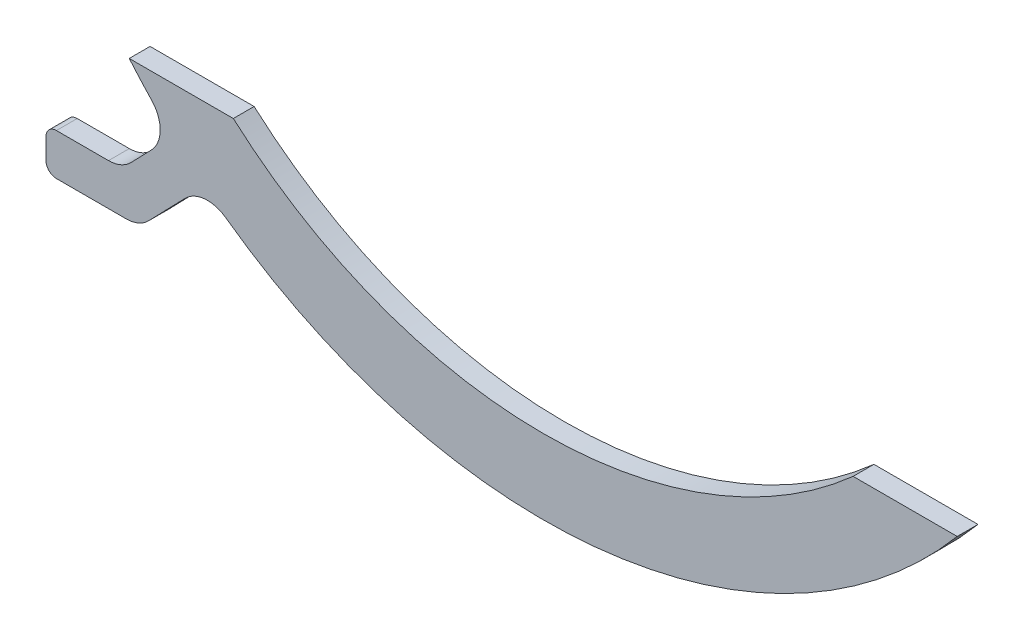
SolidWorks part; units mm, degrees
ref_plane "Front" through (0, 0, 0) normal (0, 0, 1) x (1, 0, 0)
ref_plane "Top" through (0, 0, 0) normal (0, 1, 0) x (1, 0, 0)
ref_plane "Right" through (0, 0, 0) normal (1, 0, 0) x (0, 0, -1)
sketch "Sketch1" plane through (0, 0, 0) normal (0, 0, 1) x (1, 0, 0)
  line L0 (243.078, -3.175) -> (211.328, -3.175)
  line L1 (224.028, -3.175) -> (252.603, -3.175) construction
  line L2 (-9.525, -3.175) -> (22.225, -3.175)
  line L3 (9.525, -3.175) -> (-25.4, -3.175) construction
  line L6 (9.525, -3.175) -> (22.225, -3.175) construction
  arc A0 (243.078, -3.175) -> (-9.525, -3.175) centre (116.7765, 103.1544) cw
  arc A1 (211.328, -3.175) -> (22.225, -3.175) centre (116.7765, 103.1544) cw
  dimension "D5" = 165.1
  dimension "D1" = 12.7
  dimension "D2" = 31.75
  dimension "D3" = 12.7
extrude "Extrude1" add sketch "Sketch1" along normal mid plane 6.35
sketch "Sketch2" plane through (0, 0, -3.175) normal (0, 0, -1) x (-1, 0, 0)
  line L0 (34.925, -46.0375) -> (6.4319, -46.0375)
  line L1 (6.4319, -46.0375) -> (-13.3777, -25.5573)
  line L2 (34.925, -46.0375) -> (34.925, -33.3375)
  line L3 (34.925, -33.3375) -> (11.8167, -33.3375)
  line L4 (11.8167, -33.3375) -> (-3.7768, -17.2161)
  line L5 (34.925, 6.35) -> (34.925, 212.725) construction
  line L7 (26.0985, 22.225) -> (26.0985, 38.1) construction
  line L10 (-211.328, -3.175) -> (-243.078, -3.175)
  line L11 (9.525, -3.175) -> (-22.225, -3.175)
  arc A1 (-243.078, -3.175) -> (9.525, -3.175) centre (-116.7765, 103.1544) ccw construction
  arc A4 (-211.328, -3.175) -> (-22.225, -3.175) centre (-116.7765, 103.1544) ccw
  arc A5 (-243.078, -3.175) -> (9.525, -3.175) centre (-116.7765, 103.1544) ccw
  arc A7 (-13.3777, -25.5573) -> (-3.7768, -17.2161) centre (-116.7765, 103.1544) ccw
  point P15 (26.0985, 30.1625)
  dimension "D1" = 12.7
  dimension "D2" = 76.2
  dimension "D3" = 12.7
  dimension "D4" = 0
extrude "Extrude2" add sketch "Sketch2" against normal up to surface (6.35 mm away) up to face at (116.7765, -26.8573, 3.175)
fillet "Fillet1" radius 9.525 4 edges at (3.7768, -17.2161, 0) (-11.8167, -33.3375, 0) (13.3777, -25.5573, 0) (-6.4319, -46.0375, 0)
fillet "Fillet2" radius 3.175 2 edges at (-34.925, -33.3375, 0) (-34.925, -46.0375, 0)
